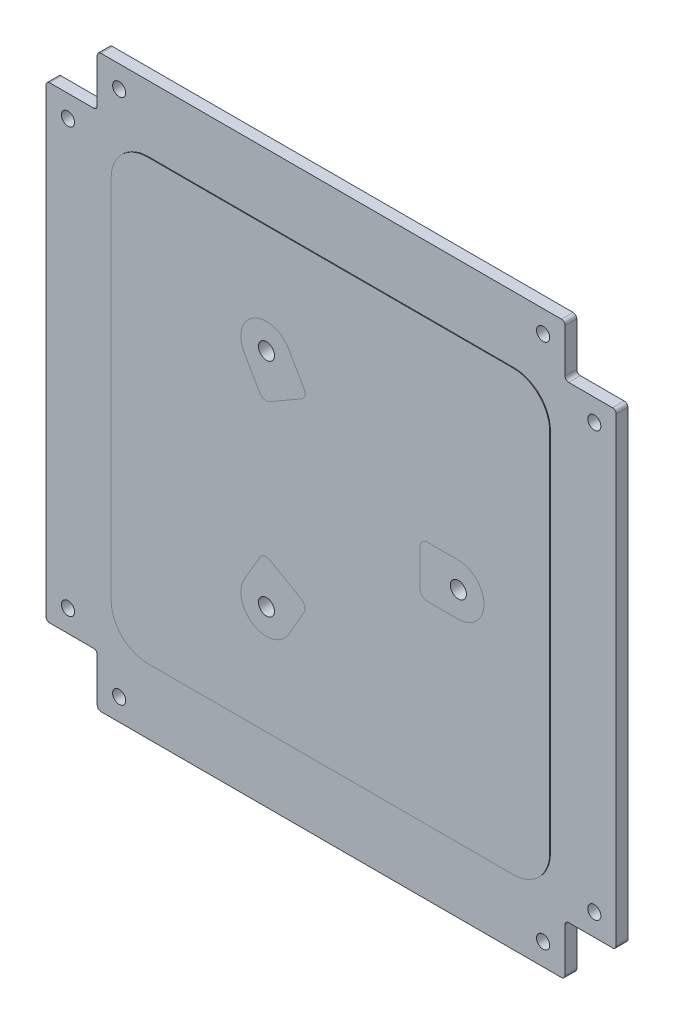
SolidWorks part; units mm, degrees
material "PET"
ref_plane "Front Plane" through (0, 0, 0) normal (0, 0, 1) x (1, 0, 0)
ref_plane "Top Plane" through (0, 0, 0) normal (0, 1, 0) x (1, 0, 0)
ref_plane "Right Plane" through (0, 0, 0) normal (1, 0, 0) x (0, 0, -1)
sketch "Sketch1" plane through (0, 0, 0) normal (0, 0, 1) x (1, 0, 0)
  line L0 (-32, 38.5) -> (-32, 32.5)
  line L1 (-31.5, -39) -> (31.5, -39)
  line L2 (-39, 31.5) -> (-39, -31.5)
  line L3 (-31.5, 39) -> (31.5, 39)
  line L4 (39, -31.5) -> (39, 31.5)
  line L5 (32, -38.5) -> (32, -32.5)
  line L6 (32.5, -32) -> (38.5, -32)
  line L7 (-32.5, 32) -> (-38.5, 32)
  line L8 (32, 38.5) -> (32, 32.5)
  line L9 (32.5, 32) -> (38.5, 32)
  line L10 (-38.5, -32) -> (-32.5, -32)
  line L11 (-32, -32.5) -> (-32, -38.5)
  line L12 (-32.5, -32.5) -> (32.5, 32.5) construction
  line L13 (32.5, -32.5) -> (-32.5, 32.5) construction
  arc A0 (-31.5, 39) -> (-32, 38.5) centre (-31.5, 38.5) ccw
  arc A1 (31.5, 39) -> (32, 38.5) centre (31.5, 38.5) cw
  arc A2 (32, 32.5) -> (32.5, 32) centre (32.5, 32.5) ccw
  arc A3 (38.5, 32) -> (39, 31.5) centre (38.5, 31.5) cw
  arc A4 (31.5, -39) -> (32, -38.5) centre (31.5, -38.5) ccw
  arc A5 (32.5, -32) -> (32, -32.5) centre (32.5, -32.5) ccw
  arc A6 (38.5, -32) -> (39, -31.5) centre (38.5, -31.5) ccw
  arc A7 (-32, -38.5) -> (-31.5, -39) centre (-31.5, -38.5) ccw
  arc A8 (-32, -32.5) -> (-32.5, -32) centre (-32.5, -32.5) ccw
  arc A9 (-39, -31.5) -> (-38.5, -32) centre (-38.5, -31.5) ccw
  arc A10 (-38.5, 32) -> (-39, 31.5) centre (-38.5, 31.5) ccw
  arc A11 (-32.5, 32) -> (-32, 32.5) centre (-32.5, 32.5) ccw
  point P0 (0, 0)
  dimension "D4" = 0.5
  dimension "D1" = 7
  dimension "D2" = 7
  dimension "D3" = 7
  dimension "D5" = 7
  dimension "D6" = 7
  dimension "D7" = 7
  dimension "D8" = 7
  dimension "D9" = 7
  dimension "D10" = 78
  dimension "D11" = 78
extrude "Boss-Extrude1" add sketch "Sketch1" along normal blind 1.6
sketch "Esboço1" plane through (0, 0, 1.6) normal (0, 0, 1) x (1, 0, 0)
  line L1 (-25, -30) -> (25, -30)
  line L2 (-30, -25) -> (-30, 25)
  line L3 (-25, 30) -> (25, 30)
  line L4 (30, -25) -> (30, 25)
  line L5 (-25, -25) -> (25, 25) construction
  line L6 (-25, 25) -> (25, -25) construction
  arc A0 (-30, 25) -> (-25, 30) centre (-25, 25) cw
  arc A1 (25, 30) -> (30, 25) centre (25, 25) cw
  arc A2 (30, -25) -> (25, -30) centre (25, -25) cw
  arc A3 (-25, -30) -> (-30, -25) centre (-25, -25) cw
  point P0 (0, 0)
  dimension "D1" = 5
  dimension "D2" = 60
  dimension "D3" = 60
extrude "Boss-Extrude2" add sketch "Esboço1" along normal blind 0.1
hole_wizard "M1.6 Hole1-FixingStructure" positions "Sketch3" profile "Sketch2" hole size "M1.6" standard "DIN"
sketch "Sketch3" plane through (0, 0, 0) normal (0, 0, -1) x (-1, 0, 0)
  line L0 (-31.5, 39) -> (31.5, 39) construction
  line L1 (31.5, -39) -> (-31.5, -39) construction
  line L2 (-39, -31.5) -> (-39, 31.5) construction
  line L3 (39, 31.5) -> (39, -31.5) construction
  line L4 (-31.5, 39) -> (31.5, 39) construction
  line L5 (31.5, -39) -> (-31.5, -39) construction
  line L6 (39, 31.5) -> (39, -31.5) construction
  line L7 (-39, -31.5) -> (-39, 31.5) construction
  point P0 (-29, 36)
  point P2 (29, 36)
  point P4 (-29, -36)
  point P6 (29, -36)
  point P20 (36, 29)
  point P22 (36, -29)
  point P24 (-36, -29)
  point P26 (-36, 29)
  dimension "D1" = 3
  dimension "D2" = 3
  dimension "D3" = 10
  dimension "D4" = 10
  dimension "D5" = 10
  dimension "D6" = 10
  dimension "D7" = 3
  dimension "D8" = 3
sketch "Sketch2" plane through (29, 36, 0) normal (1, 0, 0) x (0, 1, 0)
  line L0 (0, 0) -> (0, 200.5408)
  line L1 (0, 200.5408) -> (0.9, 200)
  line L2 (0.9, 200) -> (0.9, 0)
  line L5 (0.9, 0) -> (0, 0)
  line L10 (0, 200.5408) -> (-0.9, 200) construction
  line L11 (0, -6.35) -> (0, 107.95) construction
  dimension "Hole Dia." = 1.8
  dimension "Hole Depth" = 200
  dimension "Drill Angle" = 118
sketch "Sketch4" plane through (0, 0, 1.7) normal (0, 0, 1) x (1, 0, 0)
  circle A0 centre (-8.75, 15.1554) radius 1.1 construction
  circle A1 centre (-8.75, -15.1554) radius 1.1 construction
  circle A2 centre (17.5, 0) radius 1.1 construction
  circle A3 centre (-8.75, 15.1554) radius 1.1
  circle A4 centre (-8.75, -15.1554) radius 1.1
  circle A5 centre (17.5, 0) radius 1.1
extrude "Cut-Extrude1" cut sketch "Sketch4" against normal up to surface (1.7 mm away) up to face at (28.1, 36, 0)
sketch "Sketch5" plane through (0, 0, 1.7) normal (0, 0, 1) x (1, 0, 0)
  line L4 (-4.4682, -12.7391) -> (-8.7983, -10.2391) construction
  line L6 (-3.9682, -11.8731) -> (-8.2983, -9.3731)
  line L7 (-3.9682, -11.8731) -> (-8.2983, -9.3731) construction
  line L8 (-3.8564, -13.6795) -> (-5.7189, -16.9054)
  line L9 (-11.7811, -13.4054) -> (-9.9186, -10.1795)
  line L10 (-3.6022, -13.2391) -> (-5.7189, -16.9054)
  line L11 (-11.7811, -13.4054) -> (-9.6643, -9.7391)
  line L12 (-8.2983, 9.3731) -> (-3.9682, 11.8731)
  line L13 (-9.6643, 9.7391) -> (-11.7811, 13.4054)
  line L14 (-5.7189, 16.9054) -> (-3.6022, 13.2391)
  line L15 (-8.7983, 10.2391) -> (-4.4682, 12.7391) construction
  line L16 (12.2665, 2.5) -> (12.2665, -2.5)
  line L17 (13.2665, 3.5) -> (17.5, 3.5)
  line L18 (17.5, -3.5) -> (13.2665, -3.5)
  line L19 (13.2665, 2.5) -> (13.2665, -2.5) construction
  arc A2 (-3.6022, -13.2391) -> (-3.9682, -11.8731) centre (-4.4682, -12.7391) ccw
  arc A3 (-11.7811, -13.4054) -> (-5.7189, -16.9054) centre (-8.75, -15.1554) ccw
  arc A4 (-11.7811, -13.4054) -> (-5.7189, -16.9054) centre (-8.75, -15.1554) ccw
  arc A5 (-9.6643, -9.7391) -> (-8.2983, -9.3731) centre (-8.7983, -10.2391) cw
  arc A6 (-9.6643, 9.7391) -> (-8.2983, 9.3731) centre (-8.7983, 10.2391) ccw
  arc A7 (-5.7189, 16.9054) -> (-11.7811, 13.4054) centre (-8.75, 15.1554) ccw
  arc A8 (-3.6022, 13.2391) -> (-3.9682, 11.8731) centre (-4.4682, 12.7391) cw
  arc A9 (13.2665, 3.5) -> (12.2665, 2.5) centre (13.2665, 2.5) ccw
  arc A10 (17.5, -3.5) -> (17.5, 3.5) centre (17.5, 0) ccw
  arc A11 (13.2665, -3.5) -> (12.2665, -2.5) centre (13.2665, -2.5) cw
  point P41 (0, 0)
  dimension "D3" = 1
  dimension "D1" = 1
  dimension "D2" = 1
  dimension "D4" = 3
split line "Split Line1"
